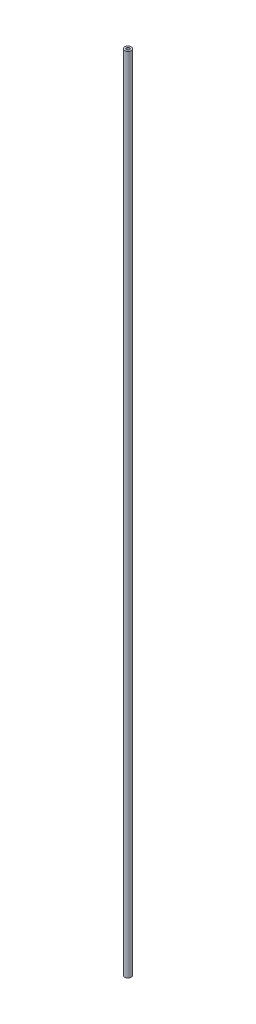
SolidWorks part; units mm, degrees
ref_plane "Front Plane" through (0, 0, 0) normal (0, 0, 1) x (1, 0, 0)
ref_plane "Top Plane" through (0, 0, 0) normal (0, 1, 0) x (1, 0, 0)
ref_plane "Right Plane" through (0, 0, 0) normal (1, 0, 0) x (0, 0, -1)
sketch "Sketch1" plane through (0, 0, 0) normal (0, 1, 0) x (1, 0, 0)
  circle A0 centre (0, 0) radius 0.5
  circle A1 centre (0, 0) radius 1
  dimension "D1" = 2
  dimension "D2" = 1
extrude "Boss-Extrude1" add sketch "Sketch1" along normal blind 120 and the other way blind 120
